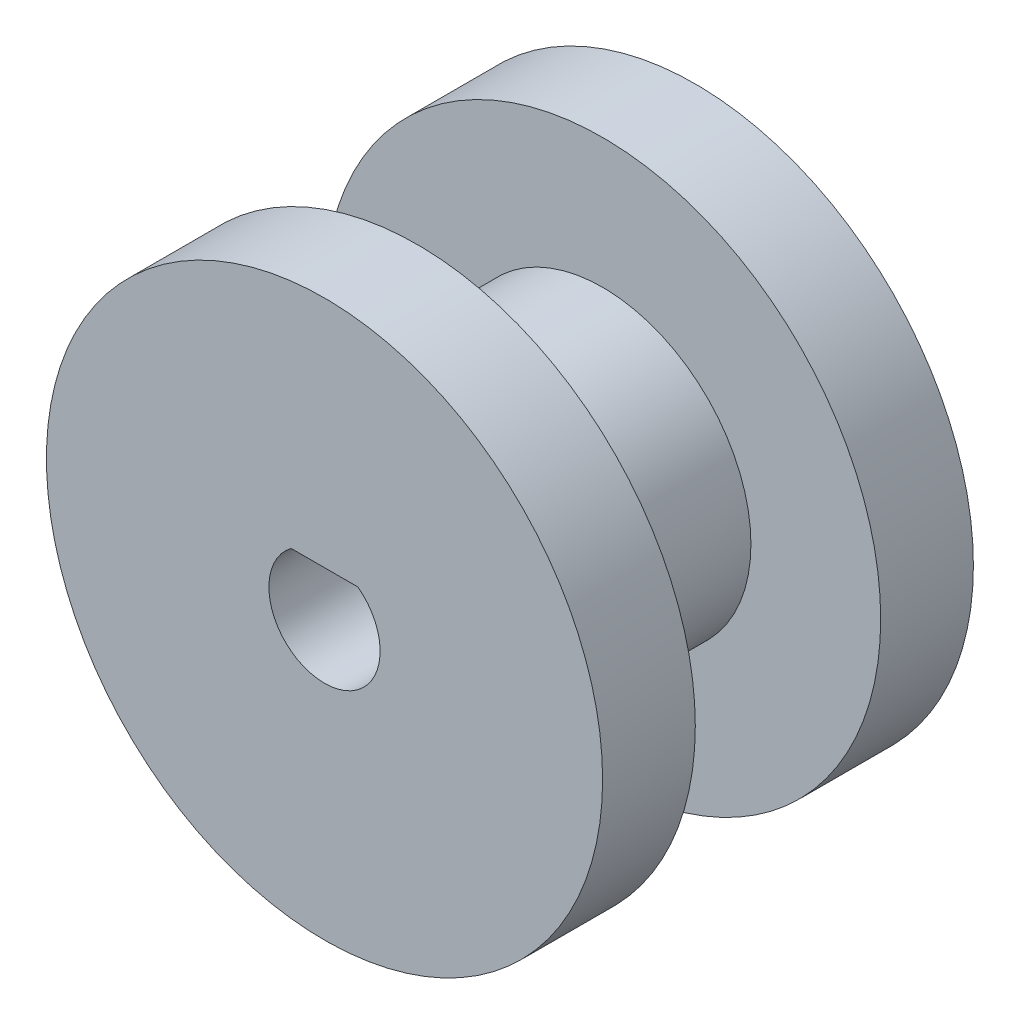
SolidWorks part; units mm, degrees
ref_plane "Plan de face" through (0, 0, 0) normal (0, 0, 1) x (1, 0, 0)
ref_plane "Plan de dessus" through (0, 0, 0) normal (0, 1, 0) x (1, 0, 0)
ref_plane "Plan de droite" through (0, 0, 0) normal (1, 0, 0) x (0, 0, -1)
sketch "Esquisse1" plane through (0, 0, 0) normal (0, 0, 1) x (1, 0, 0)
  line L0 (-1.8, 2.4) -> (1.8, 2.4)
  circle A0 centre (0, 0) radius 3
  circle A1 centre (0, 0) radius 15
  dimension "D2" = 6
  dimension "D3" = 30
  dimension "D1" = 2.4
extrude "Boss.-Extru.2" add sketch "Esquisse1" along normal blind 5 contours A1 A0 region at (-14.5757, 0, 0)
sketch "Esquisse3" plane through (0, 0, 5) normal (0, 0, 1) x (1, 0, 0)
  circle A0 centre (0, 0) radius 8
  circle A1 centre (0, 0) radius 3
  dimension "D1" = 5
extrude "Boss.-Extru.3" add sketch "Esquisse3" along normal blind 10
sketch "Esquisse4" plane through (0, 0, 15) normal (0, 0, 1) x (1, 0, 0)
  circle A0 centre (0, 0) radius 15
  circle A1 centre (0, 0) radius 3
  dimension "D1" = 30
extrude "Boss.-Extru.4" add sketch "Esquisse4" along normal blind 5
extrude "Boss.-Extru.5" add sketch "Esquisse1<4>" along normal blind 20 contours L0 A0 region at (0, 2.6422, 0)
sketch "Esquisse1<4>" plane through (0, 0, 0) normal (0, 0, 1) x (1, 0, 0) same geometry as "Esquisse1"
